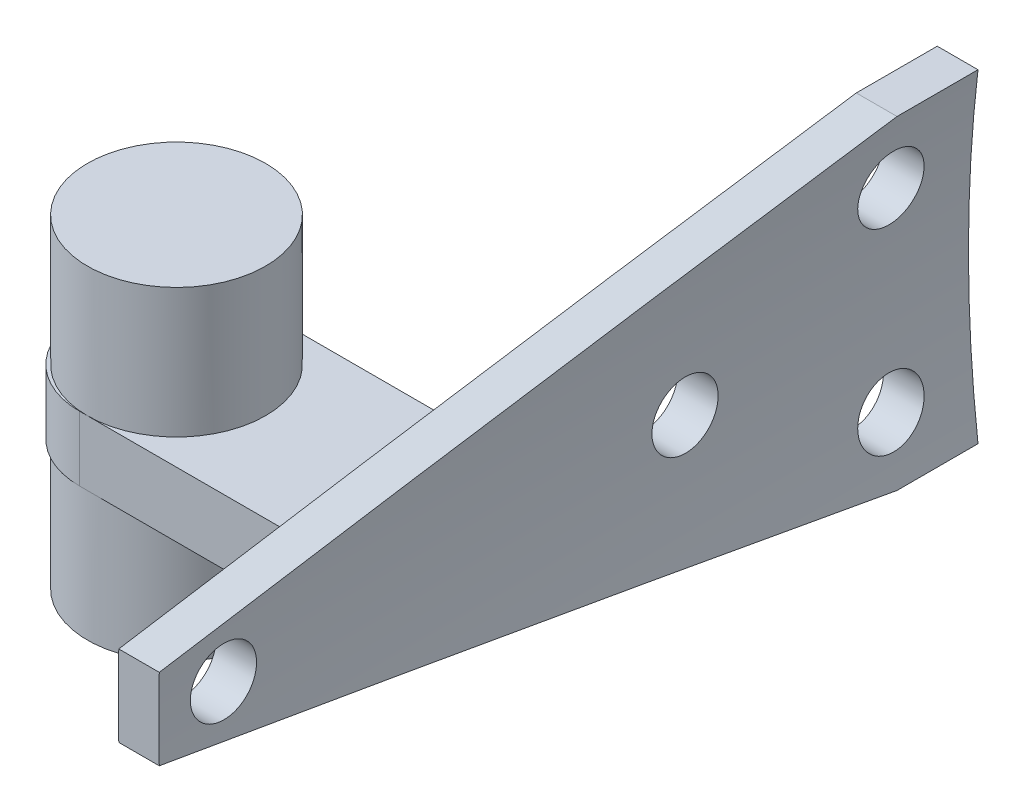
SolidWorks part; units mm, degrees
ref_plane "Front Plane" through (0, 0, 0) normal (0, 0, 1) x (1, 0, 0)
ref_plane "Top Plane" through (0, 0, 0) normal (0, 1, 0) x (1, 0, 0)
ref_plane "Right Plane" through (0, 0, 0) normal (1, 0, 0) x (0, 0, -1)
sketch "Sketch1" plane through (0, 0, 0) normal (0, 0, 1) x (1, 0, 0)
  line L0 (0, 0) -> (-52.4035, 0) construction
  line L1 (-87.0274, 10) -> (-84.5104, 10)
  line L2 (-87.0274, -10) -> (-84.5104, -10)
  arc A0 (-84.5104, 10) -> (-84.5104, -10) centre (0, 0) ccw
  arc A1 (-87.0274, 10) -> (-87.0274, -10) centre (0, 0) ccw
  dimension "D1" = 2.5
  dimension "D2" = 85.1
  dimension "D3" = 20
extrude "Boss-Extrude1" add sketch "Sketch1" along normal blind 50
sketch "Sketch2" plane through (0, 0, 0) normal (1, 0, 0) x (0, 0, -1)
  line L0 (0, 10) -> (0, -10)
  line L1 (0, 10) -> (-50, 10) construction
  line L2 (0, 10) -> (0, -10) construction
  line L3 (0, -10) -> (-50, -10) construction
  line L4 (-50, 10) -> (-50, -10) construction
  line L5 (0, -10) -> (-5, -10)
  line L6 (-5, -10) -> (-50, -2.5)
  line L7 (-50, -2.5) -> (-50, 2.5)
  line L8 (-50, 2.5) -> (-5, 10)
  line L9 (-5, 10) -> (0, 10)
  line L10 (0, 0) -> (-50.031, 0) construction
  line L12 (-88.7937, 27.6855) -> (20.3533, 27.6855)
  line L13 (-88.7937, 27.6855) -> (-88.7937, -33.0502)
  line L14 (-88.7937, -33.0502) -> (20.3533, -33.0502)
  line L15 (20.3533, 27.6855) -> (20.3533, -33.0502)
  dimension "D1" = 5
extrude "Cut-Extrude1" cut sketch "Sketch2" against normal through all
hole_wizard "#20 (0.161) Diameter Hole1" positions "Sketch5" profile "Sketch4" hole size "#20" standard "ANSI Inch" end condition through all
sketch "Sketch5" plane through (0, 0, 0) normal (1, 0, 0) x (0, 0, -1)
  line L1 (0, -10) -> (-42.3856, -10)
  line L2 (0, -10) -> (0, 10)
  line L3 (0, 10) -> (-42.3856, 10)
  line L4 (-42.3856, -10) -> (-42.3856, 10)
  line L7 (-5, 10) -> (0, 10) construction
  line L8 (0, 0) -> (-42.3856, 0)
  line L10 (-5, 6) -> (-5, -6)
  line L11 (-50, 2.5) -> (-50, -2.5) construction
  point P0 (-46, 0)
  point P164 (-5, 6)
  point P165 (-5, -6)
  point P172 (-5, 0)
  point P177 (-17.5, 0)
  dimension "D1" = 5
  dimension "D2" = 4
  dimension "D3" = 4
  dimension "D4" = 12.5
sketch "Sketch4" plane through (0, 0, 46) normal (0, 1, 0) x (0, 0, -1)
  line L0 (0, 0) -> (0, 87.6)
  line L1 (0, 87.6) -> (2.0447, 87.6)
  line L2 (2.0447, 87.6) -> (2.0447, 0)
  line L5 (2.0447, 0) -> (0, 0)
  line L11 (0, -6.35) -> (0, 107.95) construction
  dimension "Thru Hole Dia." = 4.0894
  dimension "Thru Hole Depth" = 87.6
ref_plane "Plane1" through (-86.9998, 0, 0) normal (1, 0, 0) x (0, 0, -1)
sketch "Sketch7" plane through (-86.9998, 0, -87.9998) normal (1, 0, 0) x (0, 0, -1)
  line L0 (-87.9998, 0) -> (-80.3469, 0) construction
  line L1 (-125.9998, 2) -> (-114.9998, 2)
  line L2 (-125.9998, 2) -> (-125.9998, -2)
  line L3 (-125.9998, -2) -> (-114.9998, -2)
  line L4 (-114.9998, 2) -> (-114.9998, -2)
  line L5 (-87.9998, 10) -> (-87.9998, -10) construction
  line L6 (-87.9998, -10) -> (-87.9998, 10) construction
  circle A2 centre (-133.9998, 0) radius 2.0447 construction
  point P8 (-125.9998, 0)
  dimension "D2" = 11
  dimension "D1" = 4
  dimension "D3" = 8
extrude "Boss-Extrude2" add sketch "Sketch7" against normal blind 20
fillet "Fillet1" radius 2 4 edges at (-87.5772, 2, 32.5) (-87.6, 0, 38) (-87.6, 0, 27) (-87.5772, -2, 32.5)
sketch "Sketch8" plane through (0, -2, 0) normal (0, -1, 0) x (1, 0, 0)
  line L1 (-95.9998, 27) -> (-106.9998, 27) construction
  line L2 (-95.9998, 27) -> (-95.9998, 38) construction
  line L3 (-95.9998, 38) -> (-106.9998, 38) construction
  line L4 (-106.9998, 27) -> (-106.9998, 38) construction
  line L5 (-95.9998, 27) -> (-106.9998, 38) construction
  line L6 (-95.9998, 38) -> (-106.9998, 27) construction
  circle A0 centre (-101.4998, 32.5) radius 5.5
  point P0 (-101.4998, 32.5)
extrude "Boss-Extrude3" add sketch "Sketch8" along normal blind 8 and the other way blind 12
fillet "Fillet2" radius 5 2 edges at (-106.9998, 0, 38) (-106.9998, 0, 27)
equation "\"TubeDiameter\" = 6.5433in"
